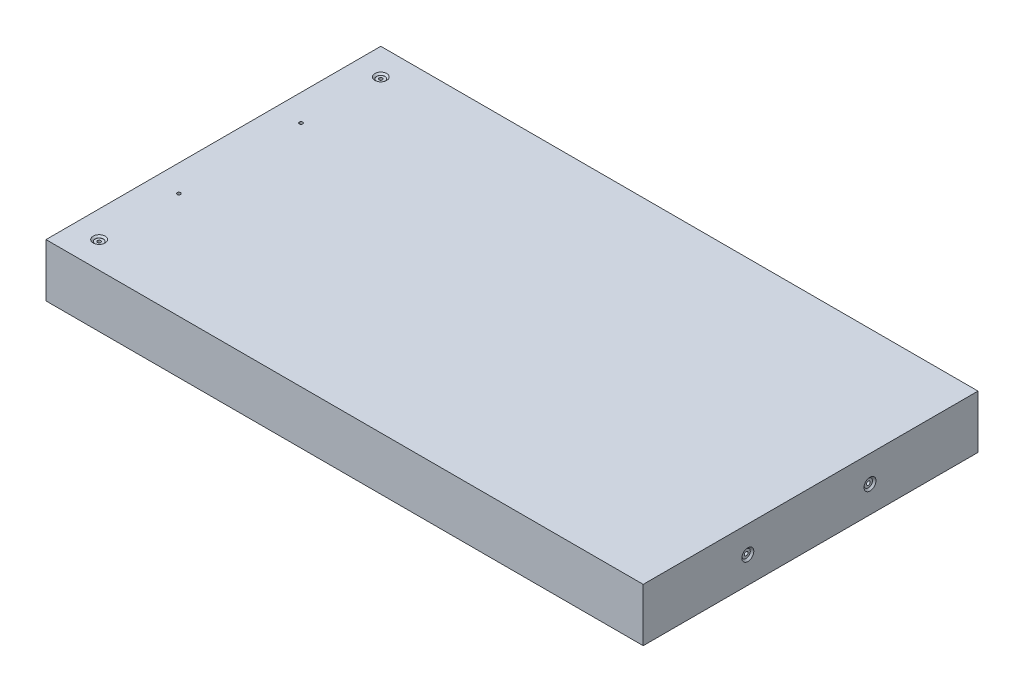
SolidWorks part; units mm, degrees
ref_plane "Front Plane" through (0, 0, 0) normal (0, 0, 1) x (1, 0, 0)
ref_plane "Top Plane" through (0, 0, 0) normal (0, 1, 0) x (1, 0, 0)
ref_plane "Right Plane" through (0, 0, 0) normal (1, 0, 0) x (0, 0, -1)
sketch "Sketch1" plane through (0, 0, 0) normal (0, 1, 0) x (1, 0, 0)
  line L1 (-142.7, 80) -> (142.7, 80)
  line L2 (-142.7, 80) -> (-142.7, -80)
  line L3 (-142.7, -80) -> (142.7, -80)
  line L4 (142.7, 80) -> (142.7, -80)
  line L5 (-142.7, 80) -> (142.7, -80) construction
  line L6 (-142.7, -80) -> (142.7, 80) construction
  point P0 (0, 0)
  dimension "D1" = 285.4
  dimension "D2" = 160
extrude "Boss-Extrude1" add sketch "Sketch1" along normal blind 25.4
hole_wizard "CBORE for #0 Binding Head Machine Screw3" positions "Sketch2" profile "Sketch3" counterbore size "#0" standard "ANSI Inch"
sketch "Sketch2" plane through (142.7, 0, 0) normal (1, 0, 0) x (0, 0, -1)
  line L0 (-80, 25.4) -> (-80, 0) construction
  point P0 (-30, 12.7)
  point P2 (28.4, 12.7)
  point P11 (-80, 12.7)
  dimension "D1" = 58.4
  dimension "D2" = 50
sketch "Sketch3" plane through (142.7, 12.7, 30) normal (0, 1, 0) x (0, 0, -1)
  line L0 (0, 0) -> (0, 30.5342)
  line L1 (0, 30.5342) -> (0.889, 30)
  line L2 (0.889, 30) -> (0.889, 0.8128)
  line L3 (0.889, 0.8128) -> (1.985, 0.8128)
  line L5 (1.985, 0.8128) -> (1.985, 0.8725)
  line L6 (1.985, 0.8725) -> (2.8575, 0)
  line L7 (2.8575, 0) -> (0, 0)
  line L8 (-1.985, 0.8725) -> (-2.8575, 0) construction
  line L10 (0, 30.5342) -> (-0.889, 30) construction
  line L11 (0, -6.35) -> (0, 107.95) construction
  dimension "Hole Dia." = 1.778
  dimension "Hole Depth" = 30
  dimension "C'Bore Dia." = 3.97
  dimension "C'Bore Depth" = 0.8128
  dimension "Near C'Sink Dia." = 5.715
  dimension "Near C'Sink Angle" = 90
  dimension "Drill Angle" = 118
hole_wizard "CBORE for #0 Binding Head Machine Screw1" positions "Sketch6" profile "Sketch7" counterbore size "#0" standard "ANSI Inch" end condition through all
sketch "Sketch6" plane through (0, 25.4, 0) normal (0, 1, 0) x (1, 0, 0)
  line L0 (-142.7, -80) -> (142.7, -80) construction
  line L1 (-142.7, 80) -> (-142.7, -80) construction
  line L2 (142.7, 80) -> (-142.7, 80) construction
  point P0 (-130, -67.3)
  point P2 (-130, 67.3)
  dimension "D1" = 12.7
  dimension "D2" = 12.7
  dimension "D3" = 12.7
sketch "Sketch7" plane through (-130, 25.4, 67.3) normal (1, 0, 0) x (0, 0, 1)
  line L0 (0, 0) -> (0, 25.4)
  line L1 (0, 25.4) -> (0.8064, 25.4)
  line L3 (0.8064, 25.4) -> (0.8065, 0.8128)
  line L4 (1.985, 0.8128) -> (0.8065, 0.8128)
  line L5 (1.985, 0.8128) -> (1.985, 0.7321)
  line L6 (1.985, 0.7321) -> (2.8575, 0)
  line L7 (2.8575, 0) -> (0, 0)
  line L8 (-1.985, 0.7321) -> (-2.8575, 0) construction
  line L11 (0, -6.35) -> (0, 107.95) construction
  dimension "Thru Hole Dia." = 1.6129
  dimension "Thru Hole Depth" = 25.4
  dimension "C'Bore Dia." = 3.97
  dimension "C'Bore Depth" = 0.8128
  dimension "Near C'Sink Dia." = 5.715
  dimension "Near C'Sink Angle" = 100
hole_wizard "CBORE for #0 Binding Head Machine Screw2" positions "Sketch8" profile "Sketch9" counterbore size "#0" standard "ANSI Inch" end condition through all
sketch "Sketch8" plane through (0, 0, 0) normal (0, -1, 0) x (-1, 0, 0)
  line L0 (-142.7, 80) -> (142.7, 80) construction
  line L1 (142.7, -80) -> (-142.7, -80) construction
  line L2 (142.7, 80) -> (142.7, -80) construction
  point P0 (130, 29.2)
  point P2 (130, -29.2)
  dimension "D1" = 50.8
  dimension "D2" = 50.8
  dimension "D3" = 12.7
  dimension "D4" = 12.7
sketch "Sketch9" plane through (-130, 0, -29.2) normal (1, 0, 0) x (0, 0, -1)
  line L0 (0, 0) -> (0, 25.4)
  line L1 (0, 25.4) -> (0.8064, 25.4)
  line L3 (0.8064, 25.4) -> (0.8065, 0.8128)
  line L4 (1.985, 0.8128) -> (0.8065, 0.8128)
  line L5 (1.985, 0.8128) -> (1.985, 0.7321)
  line L6 (1.985, 0.7321) -> (2.8575, 0)
  line L7 (2.8575, 0) -> (0, 0)
  line L8 (-1.985, 0.7321) -> (-2.8575, 0) construction
  line L11 (0, -6.35) -> (0, 107.95) construction
  dimension "Thru Hole Dia." = 1.6129
  dimension "Thru Hole Depth" = 25.4
  dimension "C'Bore Dia." = 3.97
  dimension "C'Bore Depth" = 0.8128
  dimension "Near C'Sink Dia." = 5.715
  dimension "Near C'Sink Angle" = 100
